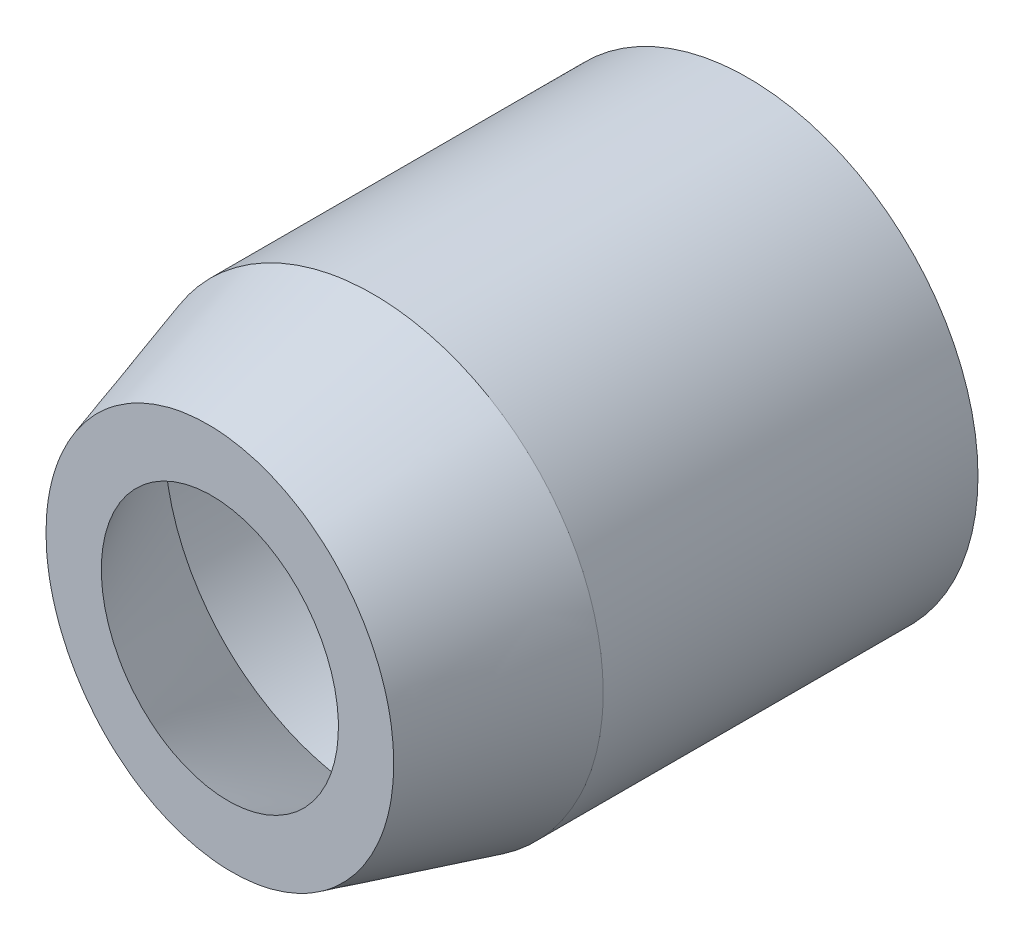
SolidWorks part; units mm, degrees
ref_plane "Front Plane" through (0, 0, 0) normal (0, 0, 1) x (1, 0, 0)
ref_plane "Top Plane" through (0, 0, 0) normal (0, 1, 0) x (1, 0, 0)
ref_plane "Right Plane" through (0, 0, 0) normal (1, 0, 0) x (0, 0, -1)
sketch "Sketch1" plane through (0, 0, 0) normal (0, 0, 1) x (1, 0, 0)
  circle A0 centre (0, 0) radius 13.5
  circle A1 centre (0, 0) radius 12.25
  dimension "D1" = 27
  dimension "D2" = 24.5
extrude "Boss-Extrude4" add sketch "Sketch1" along normal blind 22
ref_plane "Plane1" through (0, 0, 22) normal (0, 0, 1) x (1, 0, 0)
sketch "Sketch2" plane through (0, 0, 22) normal (0, 0, 1) x (1, 0, 0)
  circle A1 centre (0, 0) radius 13.5
  dimension "D2" = 27
ref_plane "Plane2" through (0, 0, 31) normal (0, 0, 1) x (1, 0, 0)
sketch "Sketch3" plane through (0, 0, 31) normal (0, 0, 1) x (1, 0, 0)
  circle A1 centre (0, 0) radius 11
  dimension "D2" = 22
sketch "Sketch4" plane through (0, 0, 22) normal (0, 0, 1) x (1, 0, 0)
  circle A0 centre (0, 0) radius 12.25
  dimension "D1" = 24.5
sketch "Sketch6" plane through (0, 0, 31) normal (0, 0, 1) x (1, 0, 0)
  line L0 (0, 0) -> (0, -25.4)
  line L1 (0, -12.1) -> (0, 12.1) construction
  dimension "D1" = 25.4
ref_plane "Plane3" through (-2.1572, 0, 30.8492) normal (-0.0698, 0, 0.9976) x (0, -1, 0)
sketch "Sketch7" plane through (-2.1572, 0, 30.8492) normal (-0.0698, 0, 0.9976) x (0, -1, 0)
  circle A0 centre (0, 2.1625) radius 11
  dimension "D1" = 22
loft "Loft3" add profiles "Sketch2", "Sketch7" connector at (13.5, 0, 22) connector at (10.9732, 0, 31.7673)
sketch "Sketch8" plane through (0, 0, 22) normal (0, 0, 1) x (1, 0, 0)
  circle A0 centre (0, 0) radius 12.25
  dimension "D1" = 24.5
sketch "Sketch9" plane through (-2.1572, 0, 30.8492) normal (-0.0698, 0, 0.9976) x (0, -1, 0)
  circle A0 centre (0, 2.1625) radius 7.5
  ellipse E1 centre (0, 2.1625) end of major axis (11, 2.1625) minor radius 10.9732 construction
  point P2 (0, 2.154)
  dimension "D1" = 15
loft "Cut-Loft3" cut profiles "Sketch4", "Sketch9" connector at (6.4072, 10.4408, 22) connector at (4.9159, 5.6538, 31.3438)
